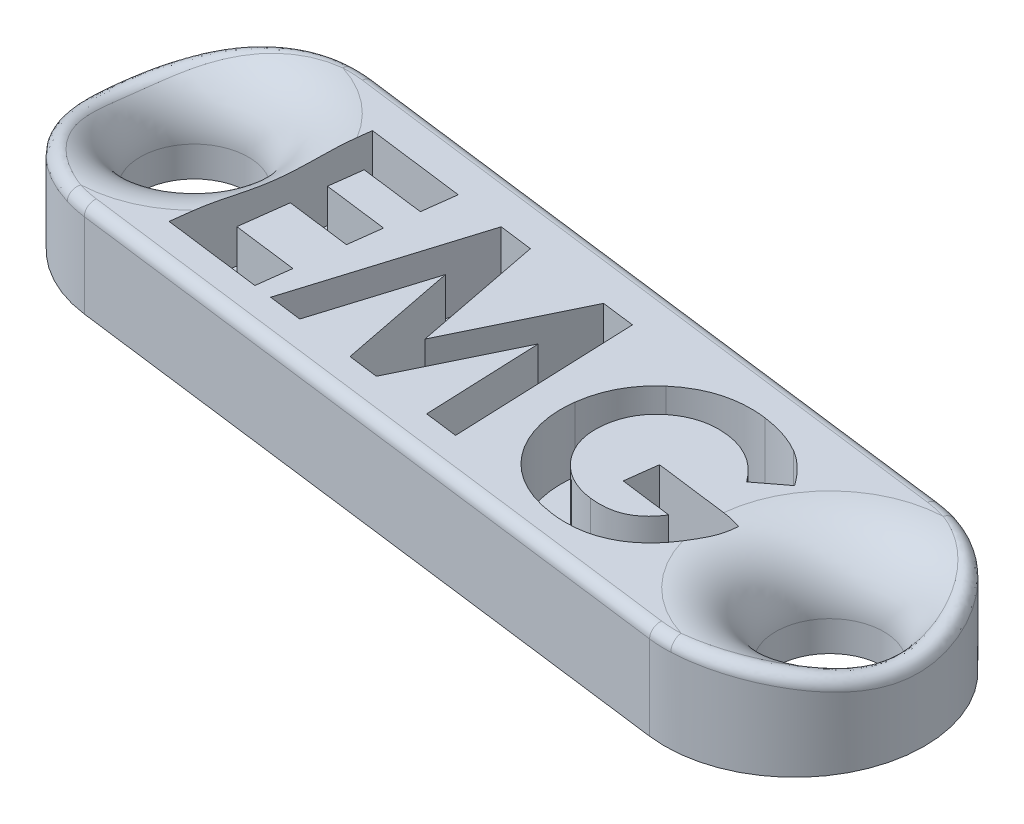
SolidWorks part; units mm, degrees
ref_plane "Front Plane" through (0, 0, 0) normal (0, 0, 1) x (1, 0, 0)
ref_plane "Top Plane" through (0, 0, 0) normal (0, 1, 0) x (1, 0, 0)
ref_plane "Right Plane" through (0, 0, 0) normal (1, 0, 0) x (0, 0, -1)
sketch "Sketch1" plane through (0, 0, 0) normal (0, 1, 0) x (1, 0, 0)
  line L0 (-7.5, 0.9601) -> (7.5, -0.9601) construction
  line L1 (-7.1191, 3.9359) -> (7.8809, 2.0156)
  line L2 (-7.8809, -2.0156) -> (7.1191, -3.9359)
  arc A0 (-7.1191, 3.9359) -> (-7.8809, -2.0156) centre (-7.5, 0.9601) ccw
  arc A1 (7.1191, -3.9359) -> (7.8809, 2.0156) centre (7.5, -0.9601) ccw
  point P2 (0, 0)
  dimension "D1" = 6
  dimension "D2" = 15
extrude "Boss-Extrude1" add sketch "Sketch1" along normal blind 2.2
sketch "Sketch2" plane through (0, 2.2, 0) normal (0, 1, 0) x (1, 0, 0)
  line L0 (-9.8025, -0.9631) -> (9.2437, -3.4013) construction
  line L1 (-7.8809, -2.0156) -> (7.1191, -3.9359) construction
  arc A0 (-7.1191, 3.9359) -> (-7.8809, -2.0156) centre (-7.5, 0.9601) ccw construction
  arc A1 (7.1191, -3.9359) -> (7.8809, 2.0156) centre (7.5, -0.9601) ccw construction
  text T0 "<b>EMG</b>\r\n" font "Century Gothic" height in points 16
  dimension "D1" = 0
  dimension "D2" = 0.8
sketch "Sketch3" plane through (0, 2.2, 0) normal (0, 1, 0) x (1, 0, 0)
  line L0 (-7.8809, -2.0156) -> (7.1191, -3.9359) construction
  circle A0 centre (-8.4312, 1.0794) radius 1.25
  circle A1 centre (8.4312, -1.0794) radius 1.25
  dimension "D1" = 2.5
  dimension "D2" = 2.5
  dimension "D3" = 3
  dimension "D4" = 3
  dimension "D5" = 8.5
  dimension "D6" = 8.5
extrude "Cut-Extrude1" cut sketch "Sketch3" against normal blind 3
extrude "Cut-Extrude2" cut sketch "Sketch2" against normal blind 1.5
fillet "Fillet1" radius 1.5 2 edges at (8.4312, 2.2, 2.3294) (-8.4312, 2.2, 0.1706)
fillet "Fillet7" radius 0.25 8 edges at (8.499, 2.2, -1.8687) (10.4995, 2.0398, 0.9076) (7.7541, 2.2, 3.9494) (-8.499, 2.2, 1.8687) (-10.4995, 2.0398, -0.9076) (-7.7541, 2.2, -3.9494) (-0.3809, 2.2, 2.9757) (0.3809, 2.2, -2.9757)
